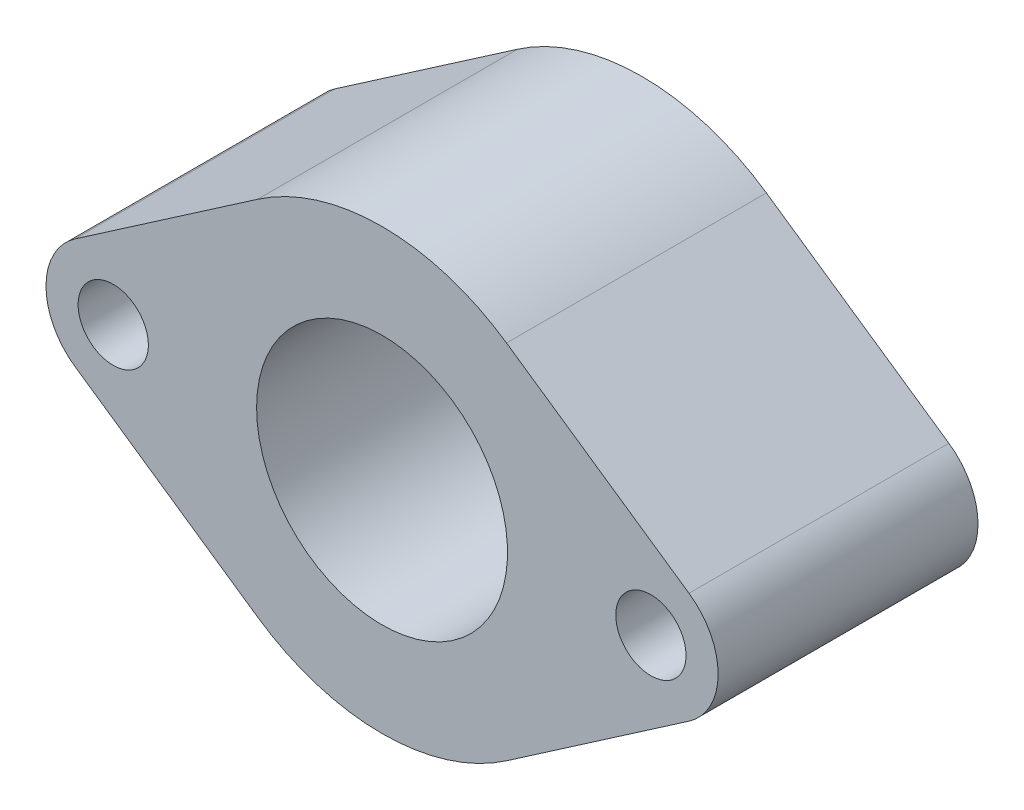
SolidWorks part; units mm, degrees
material "PET"
ref_plane "Front Plane" through (0, 0, 0) normal (0, 0, 1) x (1, 0, 0)
ref_plane "Top Plane" through (0, 0, 0) normal (0, 1, 0) x (1, 0, 0)
ref_plane "Right Plane" through (0, 0, 0) normal (1, 0, 0) x (0, 0, -1)
sketch "Sketch1" plane through (0, 0, 0) normal (0, 0, 1) x (1, 0, 0)
  line L0 (-21.7494, 3.9236) -> (-8.8194, 12.8192)
  line L1 (-21.7494, -3.9236) -> (-8.8194, -12.8192)
  line L2 (8.8194, -12.8192) -> (21.7494, -3.9236)
  line L3 (21.7494, 3.9236) -> (8.8194, 12.8192)
  arc A0 (-8.8194, -12.8192) -> (8.8194, -12.8192) centre (0, 0) ccw
  circle A1 centre (-19.05, 0) radius 2.4892
  circle A2 centre (19.05, 0) radius 2.4892
  circle A3 centre (0, 0) radius 8.89
  arc A4 (-15.2844, -2.9158) -> (-15.2844, 2.9158) centre (-19.05, 0) ccw construction
  arc A5 (21.7494, -3.9236) -> (21.7494, 3.9236) centre (19.05, 0) ccw
  arc A6 (-15.2844, -2.9158) -> (-8.8194, -12.8192) centre (0, 0) ccw construction
  arc A7 (-21.7494, -3.9236) -> (-15.2844, -2.9158) centre (-19.05, 0) ccw construction
  arc A8 (-15.2844, 2.9158) -> (-15.2844, -2.9158) centre (0, 0) ccw construction
  arc A9 (-15.2844, 2.9158) -> (-21.7494, 3.9236) centre (-19.05, 0) ccw construction
  arc A10 (-21.7494, 3.9236) -> (-21.7494, -3.9236) centre (-19.05, 0) ccw
  arc A11 (-8.8194, 12.8192) -> (-15.2844, 2.9158) centre (0, 0) ccw construction
  arc A12 (8.8194, -12.8192) -> (15.2844, -2.9158) centre (0, 0) ccw construction
  arc A13 (8.8194, 12.8192) -> (-8.8194, 12.8192) centre (0, 0) ccw
  arc A14 (15.2844, -2.9158) -> (21.7494, -3.9236) centre (19.05, 0) ccw construction
  arc A15 (15.2844, 2.9158) -> (15.2844, -2.9158) centre (19.05, 0) ccw construction
  arc A16 (15.2844, -2.9158) -> (15.2844, 2.9158) centre (0, 0) ccw construction
  arc A17 (21.7494, 3.9236) -> (15.2844, 2.9158) centre (19.05, 0) ccw construction
  arc A18 (15.2844, 2.9158) -> (8.8194, 12.8192) centre (0, 0) ccw construction
  dimension "D1" = 31.1201
  dimension "D2" = 19.05
  dimension "D3" = 19.05
  dimension "D4" = 4.9784
  dimension "D5" = 17.78
  dimension "D6" = 9.525
extrude "Boss-Extrude1" add sketch "Sketch1" along normal blind 15.24
sketch "Sketch3" plane through (0, 0, 0) normal (0, 0, -1) x (-1, 0, 0)
  line L0 (-8.8194, -12.8192) -> (-21.7494, -3.9236) construction
  line L1 (-21.7494, 3.9236) -> (-8.8194, 12.8192) construction
  line L2 (8.8194, 12.8192) -> (21.7494, 3.9236) construction
  line L3 (21.7494, -3.9236) -> (8.8194, -12.8192) construction
  line L4 (-8.8194, -12.8192) -> (-21.7494, -3.9236)
  line L5 (-21.7494, 3.9236) -> (-8.8194, 12.8192)
  line L6 (8.8194, 12.8192) -> (21.7494, 3.9236)
  line L7 (21.7494, -3.9236) -> (8.8194, -12.8192)
  line L8 (-3.2684, -0.4696) -> (-2.4639, -6.069)
  line L9 (2.4639, -6.069) -> (3.2684, -0.4696)
  arc A0 (-0.4634, -3.2693) -> (0.4634, -3.2693) centre (0, 0) ccw construction
  circle A1 centre (-19.05, 0) radius 2.4892
  circle A2 centre (19.05, 0) radius 2.4892
  circle A3 centre (-19.05, 0) radius 2.4892 construction
  circle A4 centre (19.05, 0) radius 2.4892 construction
  arc A5 (-21.7494, 3.9236) -> (-21.7494, -3.9236) centre (-19.05, 0) ccw construction
  arc A6 (8.8194, 12.8192) -> (-8.8194, 12.8192) centre (0, 0) ccw construction
  arc A7 (21.7494, -3.9236) -> (21.7494, 3.9236) centre (19.05, 0) ccw construction
  arc A8 (-8.8194, -12.8192) -> (8.8194, -12.8192) centre (0, 0) ccw construction
  arc A9 (-21.7494, 3.9236) -> (-21.7494, -3.9236) centre (-19.05, 0) ccw
  arc A10 (8.8194, 12.8192) -> (-8.8194, 12.8192) centre (0, 0) ccw
  arc A11 (21.7494, -3.9236) -> (21.7494, 3.9236) centre (19.05, 0) ccw
  arc A12 (-8.8194, -12.8192) -> (8.8194, -12.8192) centre (0, 0) ccw
  arc A13 (-2.4639, -6.069) -> (2.4639, -6.069) centre (0, -5.715) ccw
  arc A14 (-3.2684, -0.4696) -> (-0.4634, -3.2693) centre (0, 0) ccw construction
  arc A15 (-0.4634, -3.2693) -> (-2.4639, -6.069) centre (0, -5.715) ccw construction
  arc A16 (2.4639, -6.069) -> (0.4634, -3.2693) centre (0, -5.715) ccw construction
  arc A17 (0.4634, -3.2693) -> (-0.4634, -3.2693) centre (0, -5.715) ccw construction
  arc A18 (0.4634, -3.2693) -> (3.2684, -0.4696) centre (0, 0) ccw construction
  arc A19 (3.2684, -0.4696) -> (-3.2684, -0.4696) centre (0, 0) ccw
  dimension "D1" = 6.604
  dimension "D2" = 4.9784
  dimension "D3" = 5.715
extrude "Boss-Extrude2" add sketch "Sketch3" along normal blind 3.175
